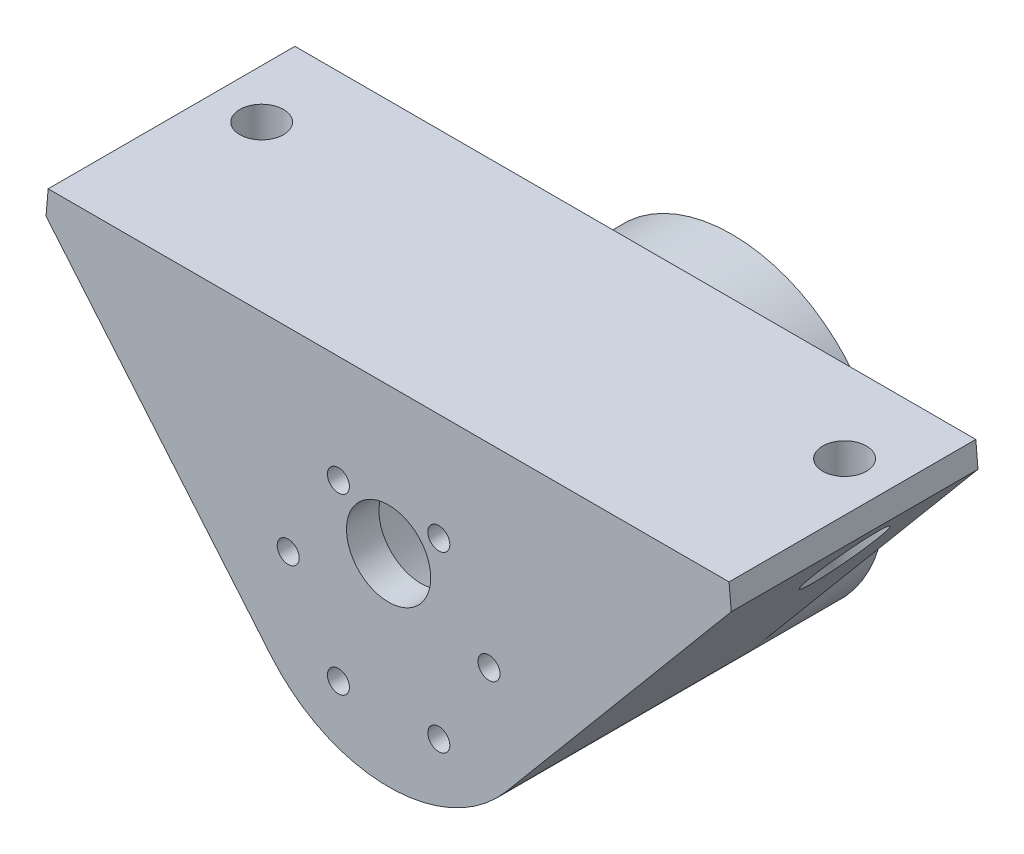
SolidWorks part; units mm, degrees
ref_plane "Front Plane" through (0, 0, 0) normal (0, 0, 1) x (1, 0, 0)
ref_plane "Top Plane" through (0, 0, 0) normal (0, 1, 0) x (1, 0, 0)
ref_plane "Right Plane" through (0, 0, 0) normal (1, 0, 0) x (0, 0, -1)
sketch "Sketch1" plane through (0, 0, 0) normal (0, 0, 1) x (1, 0, 0)
  circle A0 centre (0, 0) radius 15.5
  circle A1 centre (0, 0) radius 18.7
  circle A2 centre (0, 7.5) radius 6.5
  circle A3 centre (0, 0) radius 23.7
  point P6 (0, 0)
  dimension "D1" = 31
  dimension "D2" = 37.4
  dimension "D3" = 13
  dimension "D4" = 7.5
  dimension "D5" = 5
extrude "Boss-Extrude1" add sketch "Sketch1" against normal blind 48 contours A3 A1 region at (-23.0297, 0, 0)
extrude "Boss-Extrude2" add sketch "Sketch1<3>" along normal blind 5 contours A3 A1 | A1 A0 | A0 A2 region at (0, -1.6004, 0) region at (-18.1711, 0, 0) region at (-23.0297, 0, 0)
sketch "Sketch1<3>" plane through (0, 0, 0) normal (0, 0, 1) x (1, 0, 0) same geometry as "Sketch1"
sketch "Sketch2" plane through (0, 0, 5) normal (0, 0, 1) x (1, 0, 0)
  line L0 (0, 0) -> (-15.5, 0) construction
  circle A0 centre (0, 0) radius 15.5 construction
  circle A1 centre (0, 0) radius 15.5 construction
  point P4 (-15.5, 0)
hole_wizard "M3 Clearance Hole1" positions "Sketch2" profile "Sketch3" hole size "M3" standard "ANSI Metric" end condition through all
sketch "Sketch3" plane through (-15.5, 0, 5) normal (1, 0, 0) x (0, -1, 0)
  line L0 (0, 0) -> (0, 53)
  line L1 (0, 53) -> (1.7, 53)
  line L2 (1.7, 53) -> (1.7, 0)
  line L5 (1.7, 0) -> (0, 0)
  line L11 (0, -6.35) -> (0, 107.95) construction
  dimension "Thru Hole Dia." = 3.4
  dimension "Thru Hole Depth" = 53
pattern_circular "CirPattern1" count 6 over 360 about axis through (0, 0, -48) along (0, 0, 1) of "M3 Clearance Hole1" reverse direction yes
sketch "Sketch5" plane through (0, 0, 5) normal (0, 0, 1) x (1, 0, 0)
  line L0 (-56.1111, 30) -> (56.1111, 30)
  line L1 (-56.1111, 30) -> (-18.1553, -15.2341)
  line L2 (56.1111, 30) -> (18.1553, -15.2341)
  circle A0 centre (0, 0) radius 23.7 construction
  circle A1 centre (0, 0) radius 23.7
  point P5 (-37.7102, 30)
  circle M11 centre (0, 0) radius 23.7
  dimension "D1" = 30
  dimension "D2" = 50
extrude "Boss-Extrude3" add sketch "Sketch5" against normal blind 38.1 contours L2 L0 L1 M11 region at (0, 28.79, 5)
sketch "Sketch6" plane through (0, 30, 0) normal (0, 1, 0) x (1, 0, 0)
  line L0 (-45, 20.4) -> (45, 20.4) construction
  line L2 (-56.1111, -5) -> (56.1111, -5) construction
  point P0 (50.4709, 7.7)
  point P3 (0, 20.4)
  dimension "D1" = 90
  dimension "D2" = 25.4
hole_wizard "1/4 Clearance Hole1" positions "Sketch7" profile "Sketch8" hole size "1/4" standard "ANSI Inch" end condition through all
sketch "Sketch7" plane through (0, 30, 0) normal (0, 1, 0) x (1, 0, 0)
  point P0 (-45, 20.4)
  point P3 (45, 20.4)
sketch "Sketch8" plane through (-45, 30, -20.4) normal (1, 0, 0) x (0, 0, 1)
  line L0 (0, 0) -> (0, 53.7)
  line L1 (0, 53.7) -> (3.3782, 53.7)
  line L2 (3.3782, 53.7) -> (3.3782, 0)
  line L5 (3.3782, 0) -> (0, 0)
  line L11 (0, -6.35) -> (0, 107.95) construction
  dimension "Thru Hole Dia." = 6.7564
  dimension "Thru Hole Depth" = 53.7
ref_plane "Plane2" through (0, 25, 0) normal (0, 1, 0) x (1, 0, 0)
sketch "Sketch9" plane through (0, 25, 0) normal (0, 1, 0) x (1, 0, 0)
  circle A0 centre (-45, 20.4) radius 4.953
  circle A1 centre (45, 20.4) radius 4.953
  dimension "D1" = 9.906
  dimension "D2" = 9.906
extrude "Cut-Extrude1" cut sketch "Sketch9" against normal through all
chamfer "Chamfer1" distance 5 angle 45 2 edges at (56.1111, 30, -14.05) (-56.1111, 30, -14.05) first distance on face at (49.953, 22.661, -20.4) first distance on face at (-49.953, 22.661, -20.4)
